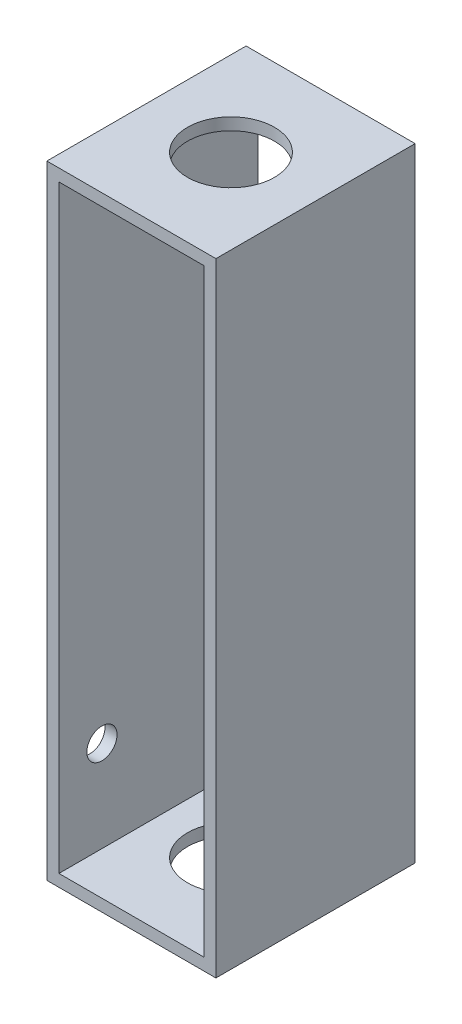
SolidWorks part; units mm, degrees
ref_plane "Front Plane" through (0, 0, 0) normal (0, 0, 1) x (1, 0, 0)
ref_plane "Top Plane" through (0, 0, 0) normal (0, 1, 0) x (1, 0, 0)
ref_plane "Right Plane" through (0, 0, 0) normal (1, 0, 0) x (0, 0, -1)
sketch "Sketch1" plane through (0, 0, 0) normal (0, 0, 1) x (1, 0, 0)
  line L1 (0, -21.6) -> (14, -21.6)
  line L2 (0, -21.6) -> (0, 30)
  line L3 (0, 30) -> (14, 30)
  line L4 (14, -21.6) -> (14, 30)
  dimension "D1" = 51.6
  dimension "D2" = 14
extrude "Boss-Extrude1" add sketch "Sketch1" along normal blind 16.5
sketch "Sketch3" plane through (0, 0, 0) normal (0, 0, 1) x (1, 0, 0)
  line L1 (0, 30) -> (14, 30)
  line L2 (0, 30) -> (0, -21.6)
  line L3 (0, -21.6) -> (14, -21.6)
  line L4 (14, 30) -> (14, -21.6)
  line L8 (1, 29) -> (13, 29)
  line L9 (13, 29) -> (13, -20.6)
  line L10 (1, -20.6) -> (13, -20.6)
  line L11 (1, 29) -> (1, -20.6)
  dimension "D1" = 1
extrude "Cut-Extrude3" cut sketch "Sketch3" against normal through all and the other way through all flip side to cut
sketch "Sketch4" plane through (0, 0, 0) normal (0, 1, 0) x (1, 0, 0)
  line L0 (0, -16.5) -> (14, 0) construction
  line L1 (0, 0) -> (7, -8.25) construction
  circle A0 centre (7, -8.25) radius 3.6
  point P7 (0, 0)
  dimension "D1" = 7.2
extrude "Cut-Extrude4" cut sketch "Sketch4" along direction (0, -1, 0) on the side against the normal blind 40.5 and the other way through all
sketch "Sketch5" plane through (0, 0, 0) normal (1, 0, 0) x (0, 0, -1)
  line L0 (-16.5, 30) -> (0, 30) construction
  circle A0 centre (-4.9397, 21.4132) radius 1.25
  circle A1 centre (-12.9397, -13.0499) radius 1.25
  dimension "D4" = 2.5
  dimension "D5" = 2.5
  dimension "D1" = 8.5868
  dimension "D2" = 8
  dimension "D3" = 34.4631
extrude "Cut-Extrude6" cut sketch "Sketch5" along direction (-1, 0, 0) on the side of the normal up to surface (1 mm away) up to face at (1, 4.2, 8.25)
ref_plane "Plane1" through (13, 29, 16.5) normal (-1, 0, 0) x (0, 0, 1)
